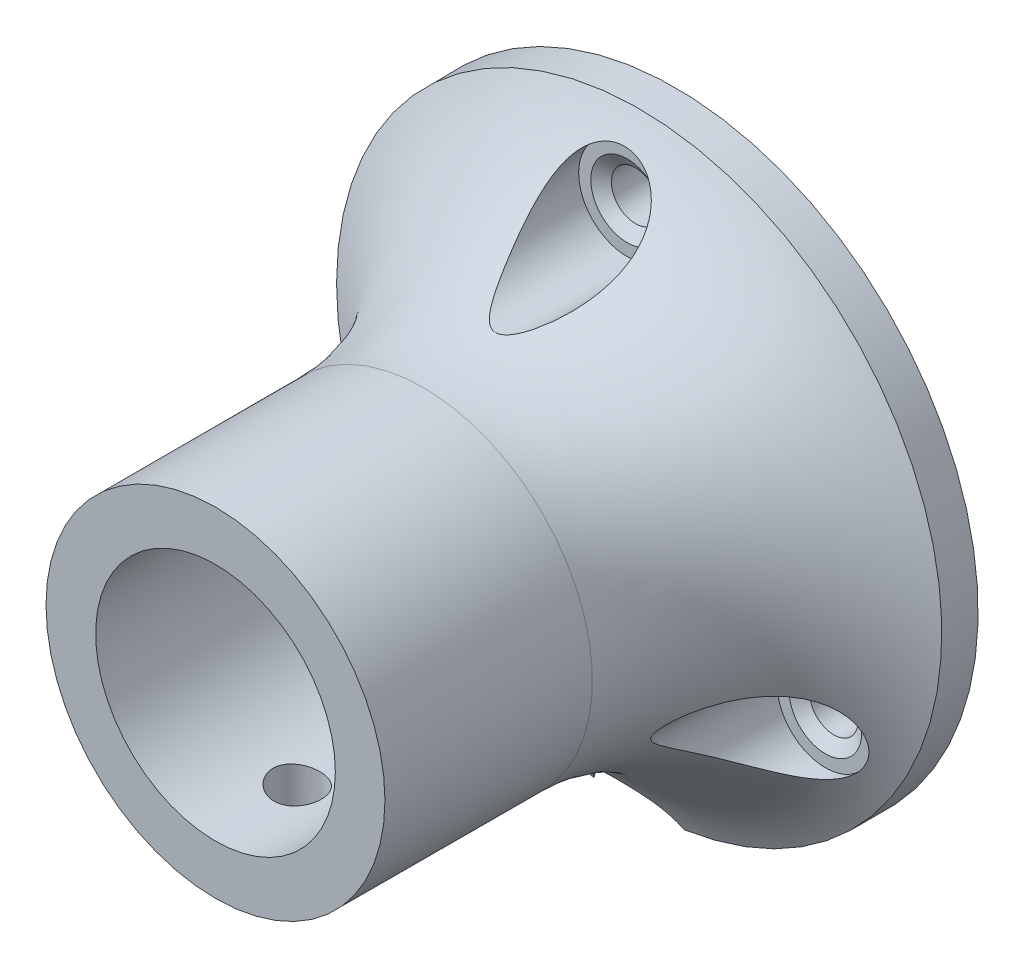
SolidWorks part; units mm, degrees
ref_plane "Спереди" through (0, 0, 0) normal (0, 0, 1) x (1, 0, 0)
ref_plane "Сверху" through (0, 0, 0) normal (0, 1, 0) x (1, 0, 0)
ref_plane "Справа" through (0, 0, 0) normal (1, 0, 0) x (0, 0, -1)
sketch "Sketch1" plane through (0, 0, 0) normal (0, 0, 1) x (1, 0, 0)
  circle A0 centre (0, 0) radius 9.9
  circle A1 centre (0, 0) radius 14
  circle A2 centre (0, 0) radius 25
extrude "Boss-Extrude1" add sketch "Sketch1" along normal blind 3 contours A2 A1 | A1 A0 region at (-13.604, 0, 0) region at (-24.2929, 0, 0)
sketch "Sketch2" plane through (0, 0, 3) normal (0, 0, 1) x (1, 0, 0)
  circle A0 centre (0, 0) radius 9.9
  circle A1 centre (0, 0) radius 14
extrude "Boss-Extrude2" add sketch "Sketch2" along normal blind 35
fillet "Fillet1" radius 20 1 edges at (14, 0, 3)
sketch "Sketch3" plane through (0, 0, 0) normal (0, 0, -1) x (-1, 0, 0)
  circle A0 centre (0, 18.9187) radius 2
  circle A1 centre (16.384, -9.4593) radius 2
  circle A2 centre (-16.384, -9.4593) radius 2
  point P9 (0, 0)
  dimension "D1" = 3
extrude "Cut-Extrude1" cut sketch "Sketch3" against normal blind 35
sketch "Sketch4" plane through (0, 0, 0) normal (0, 0, -1) x (-1, 0, 0)
  circle A0 centre (-16.384, -9.4593) radius 4
  circle A1 centre (0, 18.9187) radius 4
  circle A2 centre (16.384, -9.4593) radius 4
  point P9 (0, 0)
  dimension "D1" = 3
extrude "Cut-Extrude2" cut sketch "Sketch4" against normal blind 18 from offset 4 offset against normal yes
chamfer "Chamfer1" distance 1 angle 35 3 edges at (14.384, -9.4593, 4) (-18.384, -9.4593, 4) (-2, 18.9187, 4) first distance on face at (12.384, -9.4593, 4) first distance on face at (-20.384, -9.4593, 4) first distance on face at (-4, 18.9187, 4)
sketch "Sketch5" plane through (0, 0, 0) normal (0, 1, 0) x (1, 0, 0)
  circle A0 centre (-0.5157, -30.7313) radius 2
  circle A1 centre (0, 0) radius 4.7901
extrude "Cut-Extrude3" cut sketch "Sketch5" against normal up to next
